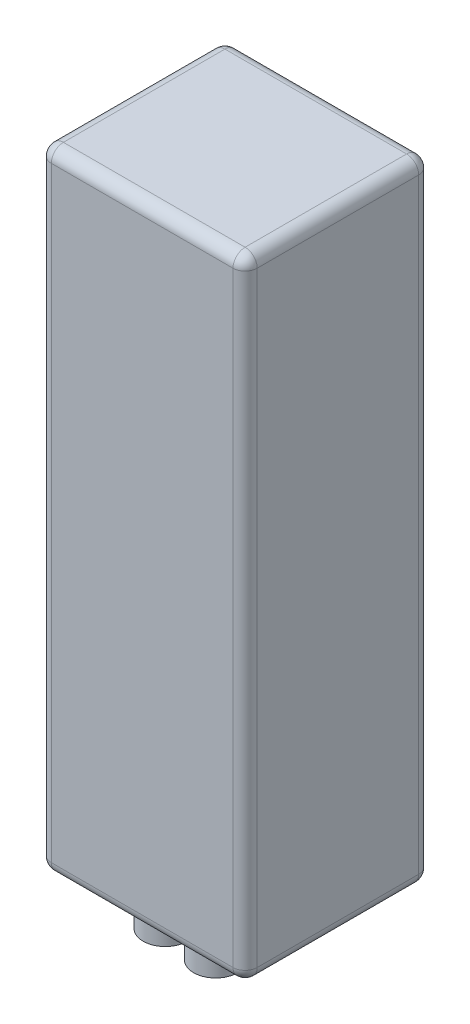
SolidWorks part; units mm, degrees
ref_plane "Front Plane" through (0, 0, 0) normal (0, 0, 1) x (1, 0, 0)
ref_plane "Top Plane" through (0, 0, 0) normal (0, 1, 0) x (1, 0, 0)
ref_plane "Right Plane" through (0, 0, 0) normal (1, 0, 0) x (0, 0, -1)
sketch "Sketch1" plane through (0, 0, 0) normal (0, 1, 0) x (1, 0, 0)
  line L1 (-39.4956, 20.7) -> (11.5044, 20.7)
  line L2 (-39.4956, 20.7) -> (-39.4956, -25.3)
  line L3 (-39.4956, -25.3) -> (11.5044, -25.3)
  line L4 (11.5044, 20.7) -> (11.5044, -25.3)
  dimension "D1" = 46
  dimension "D2" = 51
extrude "Boss-Extrude1" add sketch "Sketch1" along normal blind 156
fillet "Fillet1" radius 3 12 edges at (11.5044, 0, 2.3) (11.5044, 156, 2.3) (-39.4956, 156, 2.3) (-39.4956, 0, 2.3) (11.5044, 78, -20.7) (-13.9956, 156, -20.7) (-39.4956, 78, -20.7) (-13.9956, 0, -20.7) (-39.4956, 78, 25.3) (-13.9956, 156, 25.3) (11.5044, 78, 25.3) (-13.9956, 0, 25.3)
sketch "Sketch2" plane through (0, 0, 0) normal (0, -1, 0) x (1, 0, 0)
  circle A0 centre (-21.2412, 12.3253) radius 5.4797
  circle A1 centre (-8.249, 12.825) radius 5.4797
  point P4 (-8.249, 12.825)
  point P5 (-21.2412, 12.3253)
extrude "Boss-Extrude2" add sketch "Sketch2" along normal blind 10
